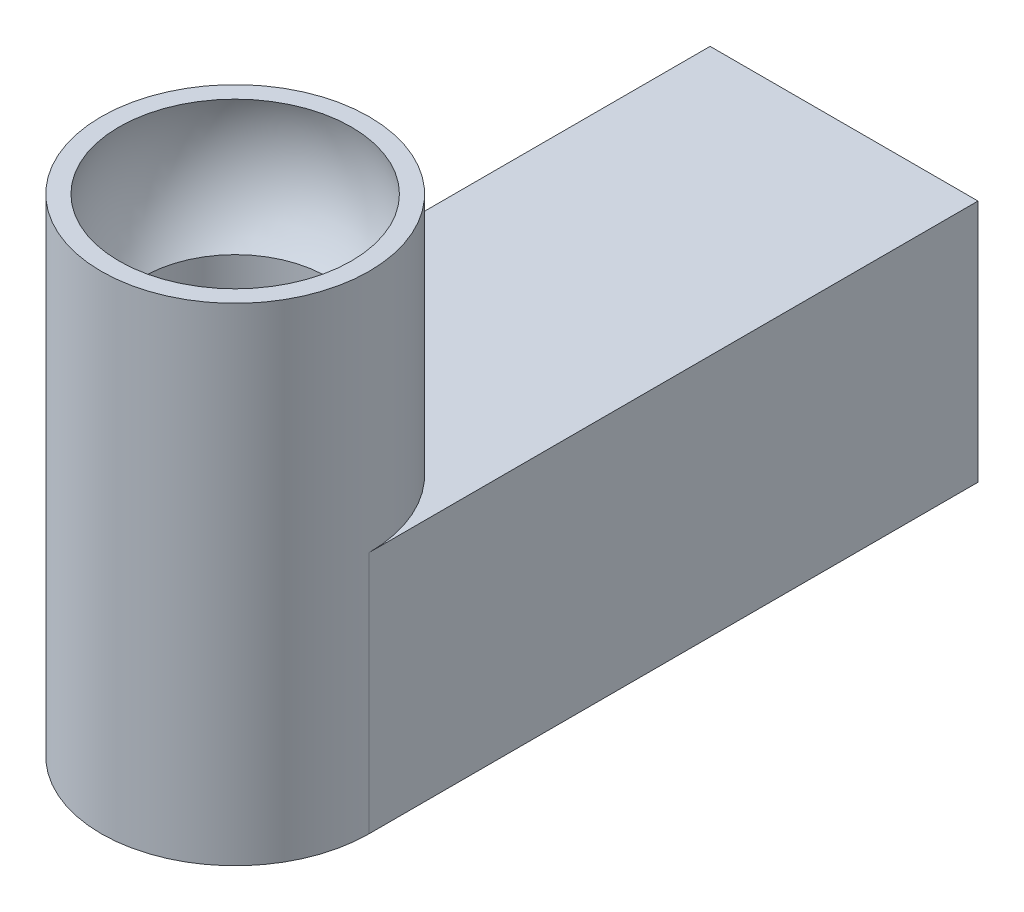
SolidWorks part; units mm, degrees
ref_plane "前视基准面" through (0, 0, 0) normal (0, 0, 1) x (1, 0, 0)
ref_plane "上视基准面" through (0, 0, 0) normal (0, 1, 0) x (1, 0, 0)
ref_plane "右视基准面" through (0, 0, 0) normal (1, 0, 0) x (0, 0, -1)
sketch "草图1" plane through (0, 0, 0) normal (0, 0, 1) x (1, 0, 0)
  line L0 (0, 0) -> (0, 6.614) construction
  line L1 (0, 6.614) -> (7.5003, 6.614) construction
  line L2 (7.5003, 6.614) -> (-7.5003, 6.614) construction
  line L3 (0, 0) -> (0, 3) construction
  line L6 (11, 3) -> (11, -17)
  line L7 (0, -17) -> (11, -17)
  line L8 (9.5394, 3) -> (11, 3)
  line L9 (0, -17) -> (0, -10)
  arc A0 (0, -10) -> (9.5394, 3) centre (0, 0) ccw
  point P9 (0, 3)
  dimension "D1" = 20
  dimension "D2" = 6.614
  dimension "D3" = 3
  dimension "D4" = 11
  dimension "D6" = 20
sketch "草图2" plane through (0, 0, 0) normal (0, 1, 0) x (1, 0, 0)
  circle A0 centre (0, 0) radius 11
sweep "扫描1" add profiles "草图1" path "草图2"
sketch "草图4" plane through (0, -17, 0) normal (0, -1, 0) x (1, 0, 0)
  line L0 (-11, 0) -> (-11, -50)
  line L1 (11, 0) -> (11, -50)
  line L2 (11, -50) -> (-11, -50)
  arc A1 (11, 0) -> (-11, 0) centre (0, 0) ccw
  dimension "D1" = 50
  dimension "D2" = 50
extrude "凸台-拉伸1" add sketch "草图4" along normal blind 20
sketch "草图5" plane through (0, 0, 0) normal (1, 0, 0) x (0, 0, -1)
  line L0 (50, -27) -> (0, -27)
  line L1 (50, -37) -> (50, -17) construction
  line L2 (0, -37) -> (0, -17) construction
  line L3 (0, -27) -> (0, 3)
  line L5 (11, 3) -> (-11, 3) construction
sketch "草图6" plane through (0, 0, -50) normal (0, 0, -1) x (-1, 0, 0)
  line L0 (0, -27) -> (0, 3) construction
  circle A0 centre (0, -27) radius 7.5
  dimension "D1" = 15
sweep "切除-扫描1" cut profiles "草图6" path "草图5"
